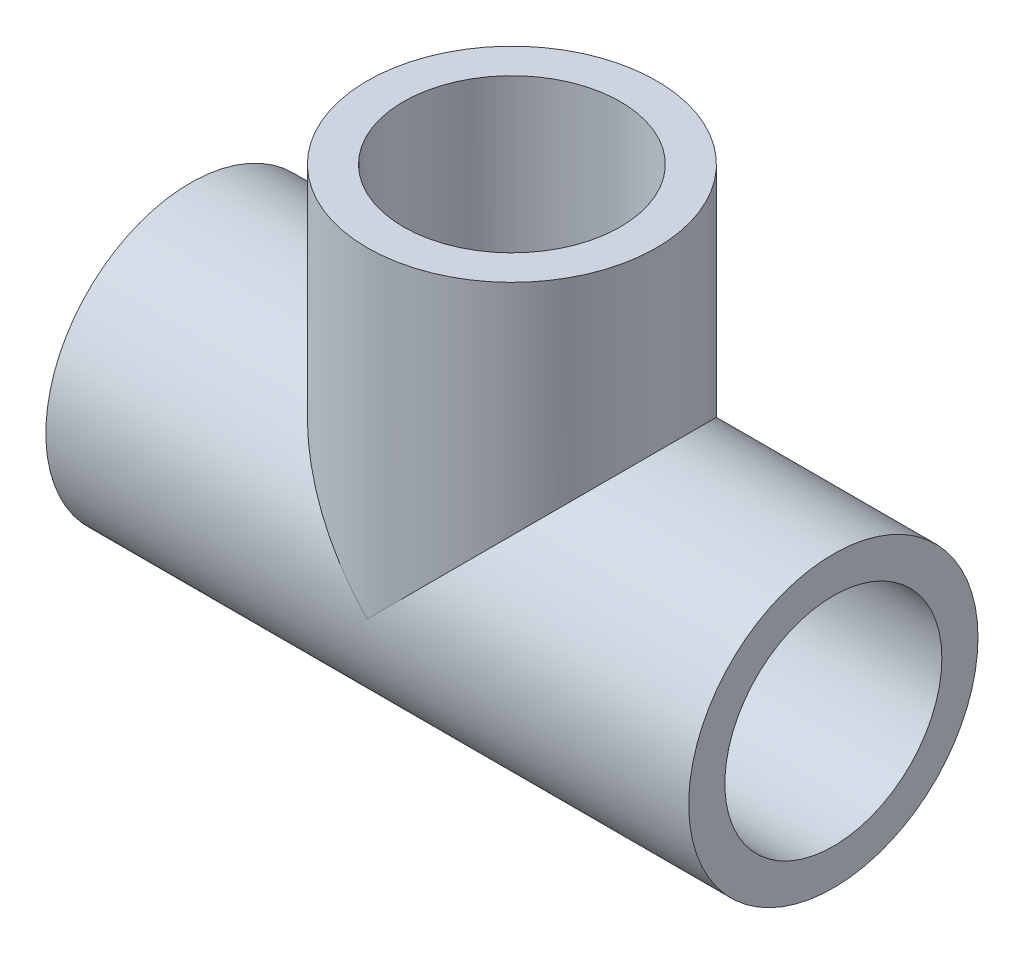
SolidWorks part; units mm, degrees
material "PVC Rigid"
ref_plane "Front Plane" through (0, 0, 0) normal (0, 0, 1) x (1, 0, 0)
ref_plane "Top Plane" through (0, 0, 0) normal (0, 1, 0) x (1, 0, 0)
ref_plane "Right Plane" through (0, 0, 0) normal (1, 0, 0) x (0, 0, -1)
sketch "Sketch1" plane through (0, 0, 0) normal (0, 0, 1) x (1, 0, 0)
  line L0 (38.1167, 0) -> (-25.9766, 0) construction
  line L1 (-23.8125, 10.7156) -> (23.8125, 10.7156)
  line L2 (-23.8125, 10.7156) -> (-23.8125, 8.0391)
  line L3 (-23.8125, 8.0391) -> (-10.3188, 8.0391)
  line L4 (-10.3188, 8.0391) -> (-10.3188, 7.8613)
  line L5 (0, 10.7156) -> (0, -56.328) construction
  line L6 (10.3188, 8.0391) -> (10.3188, 7.8613)
  line L7 (23.8125, 8.0391) -> (10.3188, 8.0391)
  line L8 (23.8125, 10.7156) -> (23.8125, 8.0391)
  line L9 (-10.3188, 7.8613) -> (10.3188, 7.8613)
  point P10 (0, 7.8613)
  dimension "Dimension-M" = 21.4312
  dimension "Socket-A" = 16.0782
  dimension "Dimension-H" = 23.8125
  dimension "Dimension-G" = 10.3187
  dimension "Socket-B" = 15.7226
revolve "Revolve1" add sketch "Sketch1" angle 360 about L0
sketch "Sketch3" plane through (0, 0, 0) normal (0, 0, 1) x (1, 0, 0)
  line L0 (0, 32.7567) -> (0, -27.7573) construction
  line L1 (0, 10.7156) -> (0, -56.328) construction
  line L2 (38.1167, 0) -> (-25.9766, 0) construction
  line L3 (8.0391, 23.8125) -> (10.7156, 23.8125)
  line L4 (8.0391, 23.8125) -> (8.0391, 10.3188)
  line L5 (7.8613, 10.3188) -> (7.8613, 0)
  line L6 (10.7156, 23.8125) -> (10.7156, 0)
  line L7 (8.0391, 10.3188) -> (7.8613, 10.3188)
  line L8 (10.7156, 0) -> (7.8613, 0)
  dimension "D1" = 21.4312
  dimension "D2" = 16.0782
  dimension "D3" = 23.8125
  dimension "D4" = 10.3187
  dimension "D5" = 15.7226
revolve "Revolve2" add sketch "Sketch3" angle 360 about L0
ref_plane "Plane1" through (-26.3525, 0, 0) normal (-1, 0, 0) x (0, 0, 1)
sketch "Sketch4" plane through (-26.3525, 0, 0) normal (-1, 0, 0) x (0, 0, 1)
  circle A0 centre (0, 0) radius 7.8613
  arc A1 (-2.8893, 7.3111) -> (2.8893, 7.3111) centre (0, 0) ccw construction
extrude "Cut-Extrude1" cut sketch "Sketch4" against normal up to surface (50.165 mm away) up to face at (23.8125, 0, -10.7156)
ref_plane "Plane2" through (0, 26.3525, 0) normal (0, 1, 0) x (-1, 0, 0)
sketch "Sketch5" plane through (0, 26.3525, 0) normal (0, 1, 0) x (-1, 0, 0)
  circle A0 centre (0, 0) radius 7.8613
  arc A1 (7.3111, 2.8893) -> (-7.3111, 2.8893) centre (0, 0) ccw construction
extrude "Cut-Extrude2" cut sketch "Sketch5" against normal up to surface (26.3525 mm away) up to plane "Top Plane"
equation "\"D1@Sketch3\" = \"Dimension-M@Sketch1\""
equation "\"D2@Sketch3\" = \"Socket-A@Sketch1\""
equation "\"D3@Sketch3\" = \"Dimension-H@Sketch1\""
equation "\"D4@Sketch3\" = \"Dimension-G@Sketch1\""
equation "\"D5@Sketch3\" = \"Socket-B@Sketch1\""
